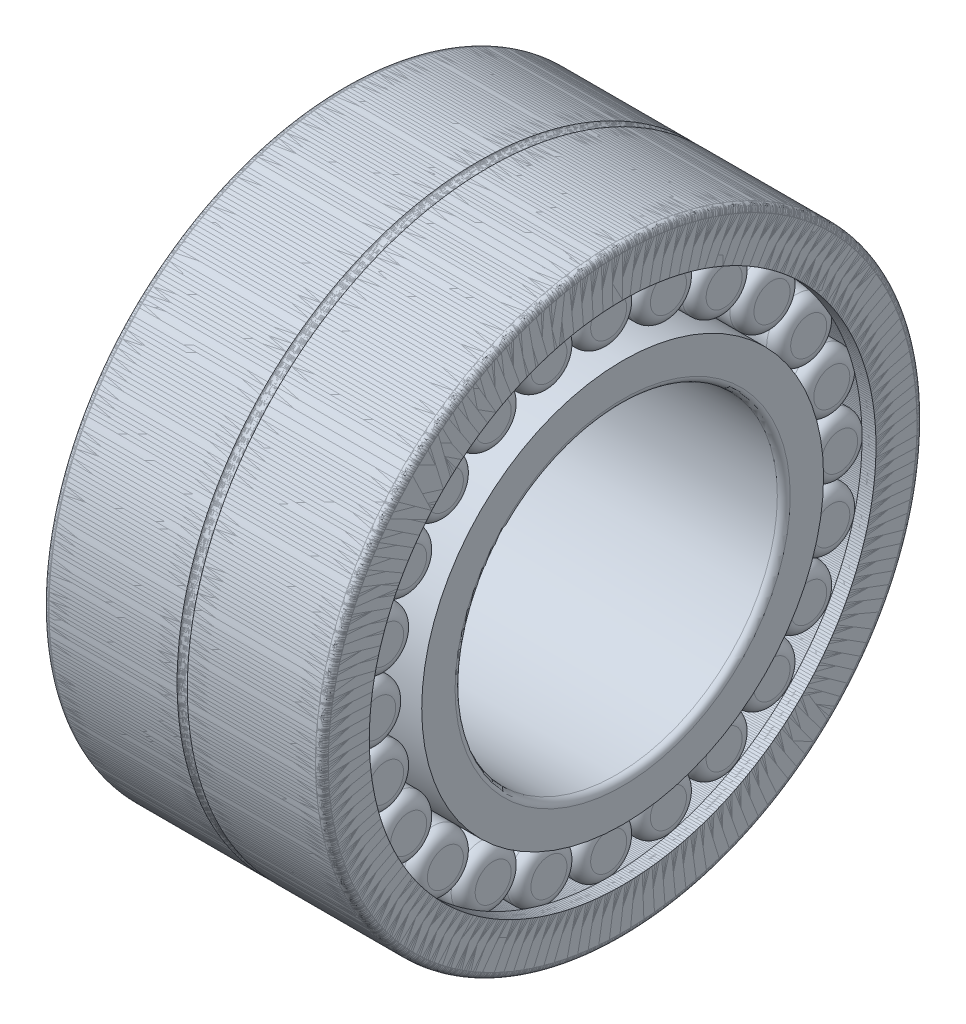
SolidWorks part; units mm, degrees
ref_plane "Plane1" through (0, 0, 0) normal (0, 0, 1) x (1, 0, 0)
ref_plane "Plane2" through (0, 0, 0) normal (0, 1, 0) x (1, 0, 0)
ref_plane "Plane3" through (0, 0, 0) normal (1, 0, 0) x (0, 0, -1)
sketch "Clipboard" plane through (0, 0, 0) normal (0, 0, 1) x (1, 0, 0)
  line L0 (-10, 0) -> (10, 0) construction
  line L1 (0, 0) -> (17.0879, -7.608)
  line L2 (0, 0) -> (21.4967, -0.3752)
  line L3 (0, 0) -> (24.2913, 0.424)
  line L4 (0, 0) -> (-22.3471, -0.7804)
  dimension "Race_OD" = 24.295
  dimension "Race_ID" = 18.705
sketch "OutRacSke" plane through (0, 0, 0) normal (0, 0, 1) x (1, 0, 0)
  line L0 (-5.85, 12.1475) -> (-5.85, 11.7981)
  line L1 (-5.85, 11.7981) -> (-6.5, 11.7981)
  line L2 (-6.5, 11.7981) -> (-6.5, 13.7)
  line L3 (-6.2, 14) -> (-0.24, 14)
  line L4 (6.5, 13.7) -> (6.5, 11.7981)
  line L5 (6.5, 11.7981) -> (5.85, 11.7981)
  line L6 (5.85, 11.7981) -> (5.85, 12.1475)
  line L7 (5.85, 12.1475) -> (-5.85, 12.1475)
  line L8 (-7.9375, 0) -> (7.9375, 0) construction
  line L9 (0.24, 14) -> (6.2, 14)
  arc A0 (-6.5, 13.7) -> (-6.2, 14) centre (-6.2, 13.7) cw
  arc A1 (6.2, 14) -> (6.5, 13.7) centre (6.2, 13.7) cw
  arc A2 (-0.24, 14) -> (0.24, 14) centre (0, 14.18) ccw
  dimension "D1" = 5.85
  dimension "Groove_Dp" = 0.3494
  dimension "Race_OD" = 24.295
  dimension "D2" = 0.18
  dimension "Cyl_Len" = 11.7
  dimension "halfWidth" = 6.5
revolve "OuterRace" add sketch "OutRacSke" angle 360 about L8 reverse direction yes
sketch "RolDetSke" plane through (0, 0, 0) normal (0, 0, 1) x (1, 0, 0)
  line L0 (-5.85, 11.5888) -> (-5.85, 10.75)
  line L1 (-5.85, 10.75) -> (5.85, 10.75)
  line L2 (5.85, 10.75) -> (5.85, 11.5888)
  line L3 (5.2908, 12.148) -> (-5.2908, 12.148)
  line L4 (-28.575, 10.75) -> (28.575, 10.75) construction
  arc A0 (5.85, 11.5888) -> (5.2908, 12.148) centre (5.2908, 11.5888) ccw
  arc A1 (-5.2908, 12.148) -> (-5.85, 11.5888) centre (-5.2908, 11.5888) ccw
  dimension "Cyl_Len" = 11.7
revolve "RollerDetailed" add sketch "RolDetSke" angle 360 about L4 reverse direction yes
ref_axis "Axis1" through (-50, 0, 0) along (1, 0, 0)
sketch "InsRacSke" plane through (0, 0, 0) normal (0, 0, 1) x (1, 0, 0)
  line L2 (-6.5, 9.3525) -> (-6.5, 7.8)
  line L4 (-6.2, 7.5) -> (6.2, 7.5)
  line L5 (6.5, 7.8) -> (6.5, 9.3525)
  line L8 (6.5, 9.3525) -> (-6.5, 9.3525)
  line L9 (-7.9375, 0) -> (7.9375, 0) construction
  arc A0 (-6.5, 7.8) -> (-6.2, 7.5) centre (-6.2, 7.8) ccw
  arc A2 (6.2, 7.5) -> (6.5, 7.8) centre (6.2, 7.8) ccw
  dimension "radius" = 0.3
  dimension "halfWidth" = 6.5
  dimension "Race_ID" = 18.705
revolve "InnerRace" add sketch "InsRacSke" angle 360 about L9 reverse direction yes
sketch "CagSpiSke" plane through (0, 0, 0) normal (0, 0, 1) x (1, 0, 0)
  line L0 (-17.1595, 0) -> (17.1595, 0) construction
  line L3 (-6.175, 10.4704) -> (6.175, 10.4704)
  line L4 (-6.175, 10.4704) -> (-6.175, 11.0296)
  line L5 (-6.175, 11.0296) -> (6.175, 11.0296)
  line L6 (6.175, 10.4704) -> (6.175, 11.0296)
pattern_circular "CirPattern1" count 24 over 360 about axis through (-7.9375, 0, 0) along (1, 0, 0) of bodies 102
equation "\"halfWidth@OutRacSke\" =  \"Width@OutRacSke\" / 2"
equation "\"CLdia@Clipboard\" =  ( \"Race_OD@Clipboard\" + \"Race_ID@Clipboard\" )  / 2"
equation "\"CLRad@RolDetSke\" = ( \"Race_OD@Clipboard\" + \"Race_ID@Clipboard\" )  / 4"
equation "\"Roller_diameter@RolDetSke\" =  ( \"Race_OD@Clipboard\" -  \"Race_ID@Clipboard\" )  / 2 + .001"
equation "\"Roller_diameter@RolSimSke\" = ( \"Race_OD@Clipboard\" -  \"Race_ID@Clipboard\" )  / 2 + .001"
equation "\"radius@RolDetSke\" = \"Roller_diameter@RolDetSke\" / 5"
equation "\"radius@RolSimSke\" = \"Roller_diameter@RolSimSke\" / 5"
equation "\"Cyl_Len@OutRacSke\" = \"Cyl_Len@RolDetSke\""
equation "\"Cyl_Len@RolSimSke\" = \"Cyl_Len@RolDetSke\""
equation "\"halfCylLen@RolDetSke\" = \"Cyl_Len@RolDetSke\" / 2"
equation "\"D1@OutRacSke\" = \"Cyl_Len@OutRacSke\" / 2"
equation "\"D2@OutRacSke\" = \"Radius@OutRacSke\" * .6"
equation "\"cage_width@CagSpiSke\" =  ( \"Cyl_Len@RolDetSke\" + \"Width@OutRacSke\" )  / 2"
equation "\"halfwidth@CagSpiSke\" = \"cage_width@CagSpiSke\" / 2"
equation "\"cage_thickness@CagSpiSke\" = \"Roller_diameter@RolDetSke\" / 5"
equation "\"d2@CagSpiSke\" = \"CLRad@RolDetSke\" * 2 - \"cage_thickness@CagSpiSke\""
equation "\"Max_count@Clipboard\" = int( 3.14159265 / atn(( \"Roller_diameter@RolDetSke\" / 2) / sqr( \"CLRad@RolDetSke\"  *  \"CLRad@RolDetSke\" - ( \"Roller_diameter@RolDetSke\" / 2) *  ( \"Roller_diameter@RolDetSke\" / 2))))"
equation "\"Max_count@Clipboard\" = ((sgn( \"Max_count@Clipboard\" - \"Count@Clipboard\" )-1)*( \"Max_count@Clipboard\" - \"Count@Clipboard\" ))/-2+ \"Count@Clipboard\""
equation "\"Bore@RolSimSke\" = \"Race_ID@Clipboard\""
equation "\"Race_ID@InsRacSke\" = \"Race_ID@Clipboard\""
equation "\"halfLength@RolSimSke\" = \"Cyl_Len@RolSimSke\" / 2"
equation "\"Race_OD@OutRacSke\" = \"Race_OD@Clipboard\""
equation "\"Width_IR@InsRacSke\" = \"Width@OutRacSke\""
equation "\"radius@InsRacSke\" = \"Radius@OutRacSke\""
